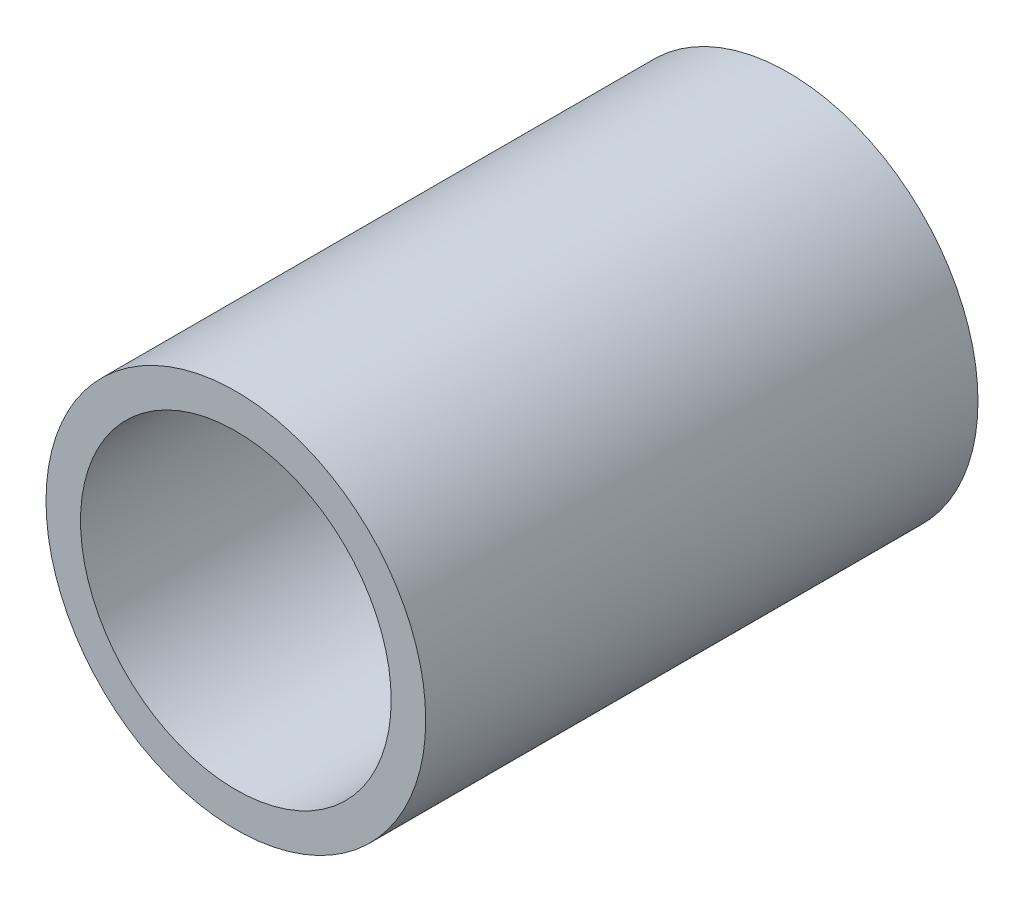
SolidWorks part; units mm, degrees
ref_plane "Front Plane" through (0, 0, 0) normal (0, 0, 1) x (1, 0, 0)
ref_plane "Top Plane" through (0, 0, 0) normal (0, 1, 0) x (1, 0, 0)
ref_plane "Right Plane" through (0, 0, 0) normal (1, 0, 0) x (0, 0, -1)
sketch "Sketch2" plane through (0, 0, 0) normal (0, 0, 1) x (1, 0, 0)
  circle A0 centre (2200, 0) radius 110
  circle A1 centre (2200, 0) radius 90
  dimension "D1" = 180
extrude "Boss-Extrude1" add sketch "Sketch2" along normal blind 160 and the other way blind 160
